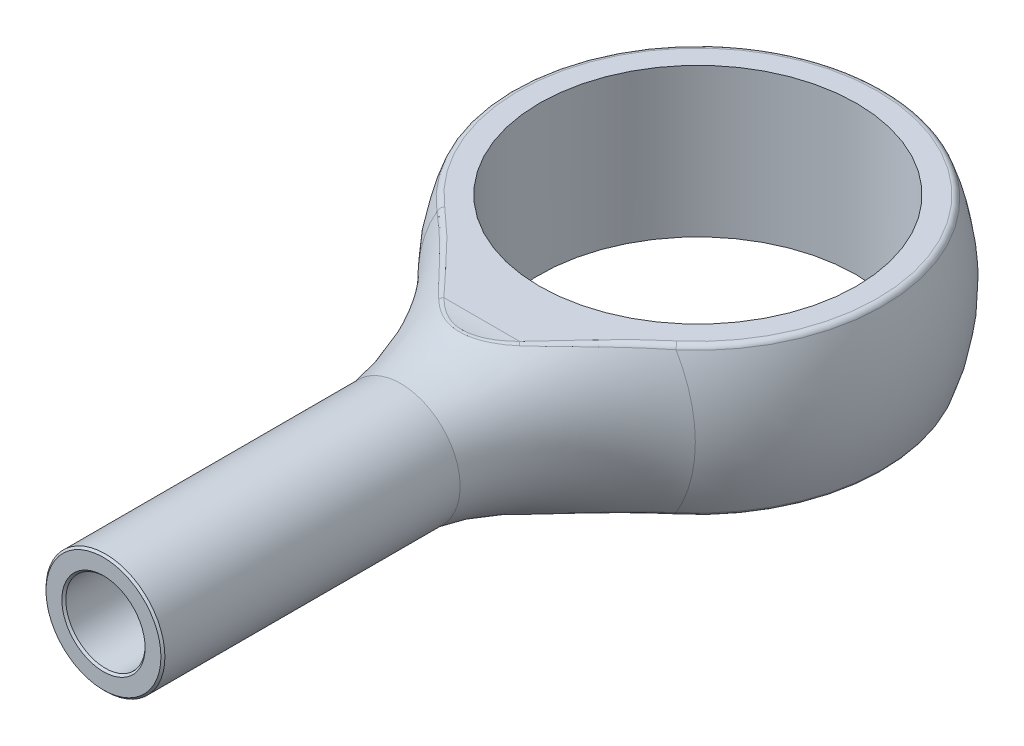
SolidWorks part; units mm, degrees
ref_plane "Front Plane" through (0, 0, 0) normal (0, 0, 1) x (1, 0, 0)
ref_plane "Top Plane" through (0, 0, 0) normal (0, 1, 0) x (1, 0, 0)
ref_plane "Right Plane" through (0, 0, 0) normal (1, 0, 0) x (0, 0, -1)
sketch "Sketch1" plane through (0, 0, 0) normal (0, 1, 0) x (1, 0, 0)
  line L0 (1.5, -15) -> (-1.5, -15)
  line L1 (1.5, -15) -> (1.5, -7.5)
  line L2 (-1.5, -15) -> (-1.5, -7.5)
  circle A0 centre (0, 0) radius 4
  circle A1 centre (0, 0) radius 5
  circle A2 centre (0, 0) radius 2 construction
  arc A3 (-1.5, -7.5) -> (-3.5029, -3.5678) centre (-8.3664, -8.5213) ccw
  arc A4 (1.5, -7.5) -> (3.5029, -3.5678) centre (8.3664, -8.5213) cw
  point P7 (0, -15)
  dimension "D1" = 10
  dimension "D2" = 8
  dimension "D3" = 4
  dimension "D4" = 15
  dimension "D5" = 3
  dimension "D6" = 7.5
sketch "Sketch2" plane through (0, 0, 0) normal (0, 1, 0) x (1, 0, 0)
  line L0 (1.5, -15) -> (-1.5, -15) construction
  line L1 (-1.5, -15) -> (-1.5, -7.5) construction
  line L2 (0, -15) -> (-1.5, -15)
  line L3 (-1.5, -15) -> (-1.5, -7.5)
  line L4 (0, 5) -> (0, -15)
  arc A0 (-1.5, -7.5) -> (-3.5029, -3.5678) centre (-8.3664, -8.5213) ccw construction
  circle A1 centre (0, 0) radius 5 construction
  arc A2 (-1.5, -7.5) -> (-3.5029, -3.5678) centre (-8.3664, -8.5213) ccw
  arc A3 (0, 5) -> (-3.5029, -3.5678) centre (0, 0) ccw
revolve "Revolve1" add sketch "Sketch2" angle 360 about L4
sketch "Sketch4" plane through (0, 0, 0) normal (1, 0, 0) x (0, 0, -1)
  line L0 (-19.0804, 10.3119) -> (12.0437, 10.3119)
  line L1 (12.0437, 10.3119) -> (12.0437, 1.875)
  line L2 (12.0437, 1.875) -> (-5.4548, 1.875)
  line L3 (-8.3227, 2.7792) -> (-19.0804, 10.3119)
  line L4 (0, 0) -> (16.4029, 0) construction
  line L5 (-8.3227, -2.7792) -> (-19.0804, -10.3119)
  line L6 (12.0437, -1.875) -> (-5.4548, -1.875)
  line L7 (12.0437, -10.3119) -> (12.0437, -1.875)
  line L8 (-19.0804, -10.3119) -> (12.0437, -10.3119)
  arc A0 (-5.4548, 1.875) -> (-8.3227, 2.7792) centre (-5.4548, 6.875) cw
  arc A1 (-5.4548, -1.875) -> (-8.3227, -2.7792) centre (-5.4548, -6.875) ccw
  dimension "D1" = 5
  dimension "D2" = 145
  dimension "D3" = 3.75
extrude "Cut-Extrude1" cut sketch "Sketch4" against normal blind 10 and the other way blind 10
sketch "Sketch5" plane through (0, 0, 0) normal (0, 1, 0) x (1, 0, 0)
  circle A0 centre (0, 0) radius 4 construction
  circle A1 centre (0, 0) radius 4
extrude "Cut-Extrude2" cut sketch "Sketch5" against normal blind 10 and the other way blind 10
fillet "Fillet1" radius 0.15 8 edges at (-0.0881, -1.903, 5.9833) (-2.0983, -1.875, 4.3547) (0, -1.875, -4.6351) (0.0881, 1.903, 5.9833) (2.0983, 1.875, 4.3547) (0, 1.875, -4.6351)
sketch "Sketch6" plane through (0, 0, 15) normal (0, 0, 1) x (1, 0, 0)
  circle A0 centre (0, 0) radius 1
  dimension "D1" = 2
extrude "Cut-Extrude3" cut sketch "Sketch6" against normal blind 5
chamfer "Chamfer1" distance 0.05 angle 45 2 edges at (-1.5, 0, 15) (1, 0, 15)
